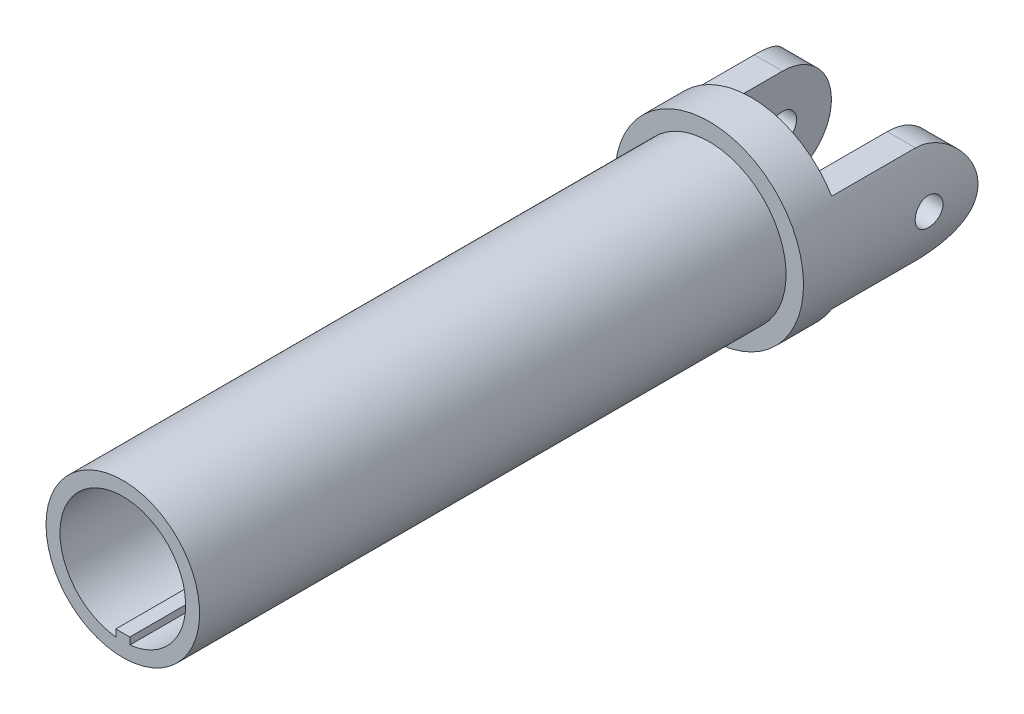
SolidWorks part; units mm, degrees
ref_plane "Front Plane" through (0, 0, 0) normal (0, 0, 1) x (1, 0, 0)
ref_plane "Top Plane" through (0, 0, 0) normal (0, 1, 0) x (1, 0, 0)
ref_plane "Right Plane" through (0, 0, 0) normal (1, 0, 0) x (0, 0, -1)
sketch "Sketch1" plane through (0, 0, 0) normal (0, 0, 1) x (1, 0, 0)
  circle A0 centre (0, 0) radius 5.5
  dimension "D1" = 11
extrude "Yoke" add sketch "Sketch1" along normal mid plane 42 contours A0
sketch "Sketch2" plane through (0, 0, -21) normal (0, 0, -1) x (-1, 0, 0)
  circle A0 centre (0, 0) radius 6.75
  dimension "D1" = 13.5
extrude "U Joint Base" add sketch "Sketch2" along normal blind 3
sketch "Sketch3" plane through (0, 0, -24) normal (0, 0, -1) x (-1, 0, 0)
  line L0 (-5.7717, 3.5) -> (-3.75, 3.5)
  line L1 (-3.75, 3.5) -> (-3.75, -3.5)
  line L2 (-3.75, -3.5) -> (-5.7717, -3.5)
  line L3 (3.75, -3.5) -> (3.75, 3.5)
  line L4 (3.75, 3.5) -> (5.7717, 3.5)
  line L5 (5.7717, -3.5) -> (3.75, -3.5)
  circle A0 centre (0, 0) radius 6.75 construction
  arc A1 (-5.7717, -3.5) -> (-5.7717, 3.5) centre (0, 0) cw
  arc A2 (5.7717, 3.5) -> (5.7717, -3.5) centre (0, 0) cw
  point P16 (0, 0)
  dimension "D2" = 7.5
  dimension "D3" = 7
  dimension "D1" = 2
extrude "U Joint Standups" add sketch "Sketch3" along normal blind 9.5
sketch "Sketch4" plane through (0, 0, 0) normal (1, 0, 0) x (0, 0, -1)
  line L0 (33.5, 3.5) -> (24, 3.5) construction
  line L1 (33.5, -3.5) -> (33.5, 3.5) construction
  line L2 (30, -3.5) -> (33.5, -3.5)
  line L3 (33.5, -3.5) -> (33.5, 0)
  line L4 (33.5, 0) -> (33.5, 3.5)
  line L5 (33.5, 3.5) -> (30, 3.5)
  line L6 (33.5, -3.5) -> (24, -3.5) construction
  arc A0 (33.5, 0) -> (30, 3.5) centre (30, 0) ccw
  arc A1 (30, -3.5) -> (33.5, 0) centre (30, 0) ccw
extrude "Standup Round" cut sketch "Sketch4" against normal through all both and the other way through all contours A1 L2 L3 | A0 L5 L4 region at (0, -2.7182, -32.7182)
sketch "Sketch5" plane through (0, 0, 0) normal (1, 0, 0) x (0, 0, -1)
  circle A0 centre (30, 0) radius 1
  dimension "D1" = 2
extrude "Ball Holes" cut sketch "Sketch5" against normal through all both and the other way through all
sketch "Sketch6" plane through (0, 0, 21) normal (0, 0, 1) x (1, 0, 0)
  line L0 (0.5, -4.4721) -> (0.5, -3.9721)
  line L1 (0.5, -3.9721) -> (-0.5, -3.9721)
  line L2 (-0.5, -3.9721) -> (-0.5, -4.4721)
  arc A0 (0.5, -4.4721) -> (-0.5, -4.4721) centre (0, 0) ccw
  dimension "D1" = 4.5
  dimension "D2" = 1
  dimension "D3" = 0.5
extrude "Keyway" cut sketch "Sketch6" against normal blind 42
